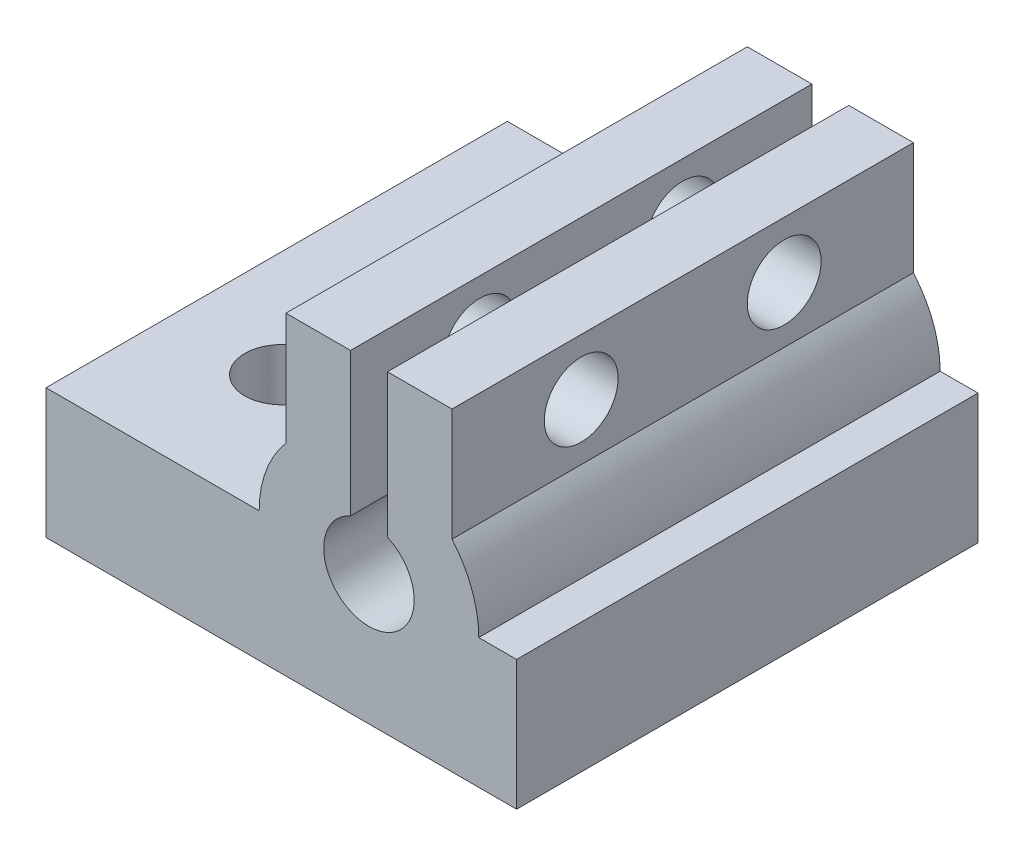
SolidWorks part; units mm, degrees
ref_plane "Front Plane" through (0, 0, 0) normal (0, 0, 1) x (1, 0, 0)
ref_plane "Top Plane" through (0, 0, 0) normal (0, 1, 0) x (1, 0, 0)
ref_plane "Right Plane" through (0, 0, 0) normal (1, 0, 0) x (0, 0, -1)
sketch "Sketch1" plane through (0, 0, 0) normal (0, 0, 1) x (1, 0, 0)
  line L0 (0, 0) -> (35, 0)
  line L1 (35, 0) -> (35, 7.03)
  line L2 (35, 7.03) -> (23.45, 7.03)
  line L3 (11.55, 7.03) -> (0, 7.03)
  line L4 (0, 7.03) -> (0, 0)
  line L5 (13, 10.9226) -> (13, 17.03)
  line L6 (13, 17.03) -> (16.5, 17.03)
  line L7 (16.5, 17.03) -> (16.5, 9.2666)
  line L8 (17.5, 0) -> (17.5, 17.03) construction
  line L9 (18.5, 9.2666) -> (18.5, 17.03)
  line L10 (18.5, 17.03) -> (22, 17.03)
  line L11 (22, 17.03) -> (22, 10.9226)
  arc A0 (23.45, 7.03) -> (22, 10.9226) centre (17.5, 7.03) ccw
  arc A1 (13, 10.9226) -> (11.55, 7.03) centre (17.5, 7.03) ccw
  arc A2 (16.5, 9.2666) -> (18.5, 9.2666) centre (17.5, 7.03) ccw
  dimension "D1" = 4.9
  dimension "D4" = 10
  dimension "D6" = 3.5
  dimension "D2" = 35
  dimension "D3" = 7.03
  dimension "D5" = 3.5
  dimension "D7" = 2
extrude "Boss-Extrude1" add sketch "Sketch1" along normal blind 25
sketch "Sketch2" plane through (22, 0, 0) normal (1, 0, 0) x (0, 0, -1)
  line L0 (-25, 13.9763) -> (0, 13.9763) construction
  line L1 (-25, 10.9226) -> (-25, 17.03) construction
  line L2 (0, 10.9226) -> (0, 17.03) construction
  circle A0 centre (-18, 13.9763) radius 2
  circle A1 centre (-7, 13.9763) radius 2
  dimension "D3" = 4
  dimension "D1" = 7
  dimension "D2" = 7
extrude "Cut-Extrude1" cut sketch "Sketch2" against normal up to surface (9 mm away) up to face at (13, 13.9763, 12.5)
sketch "Sketch3" plane through (0, 7.03, 0) normal (0, 1, 0) x (1, 0, 0)
  line L0 (29.225, -25) -> (29.225, 0) construction
  line L1 (35, -25) -> (23.45, -25) construction
  line L2 (35, 0) -> (23.45, 0) construction
  line L3 (17.5, -25) -> (17.5, 0) construction
  line L4 (0, 0) -> (35, 0) construction
  line L5 (0, -25) -> (35, -25) construction
  circle A0 centre (29.225, -18) radius 2
  circle A1 centre (29.225, -7) radius 2
  circle A2 centre (5.775, -7) radius 2
  circle A3 centre (5.775, -18) radius 2
  dimension "D2" = 7
  dimension "D3" = 4
  dimension "D1" = 7
extrude "Cut-Extrude2" cut sketch "Sketch3" against normal up to next
sketch "Sketch4" plane through (0, 7.03, 0) normal (0, 1, 0) x (1, 0, 0)
  line L0 (35, 0) -> (23.45, 0) construction
  line L1 (35, -25) -> (25.5, -25)
  line L2 (35, -25) -> (35, 0)
  line L3 (35, 0) -> (25.5, 0)
  line L4 (25.5, -25) -> (25.5, 0)
  dimension "D1" = 9.5
extrude "Cut-Extrude3" cut sketch "Sketch4" against normal up to next
